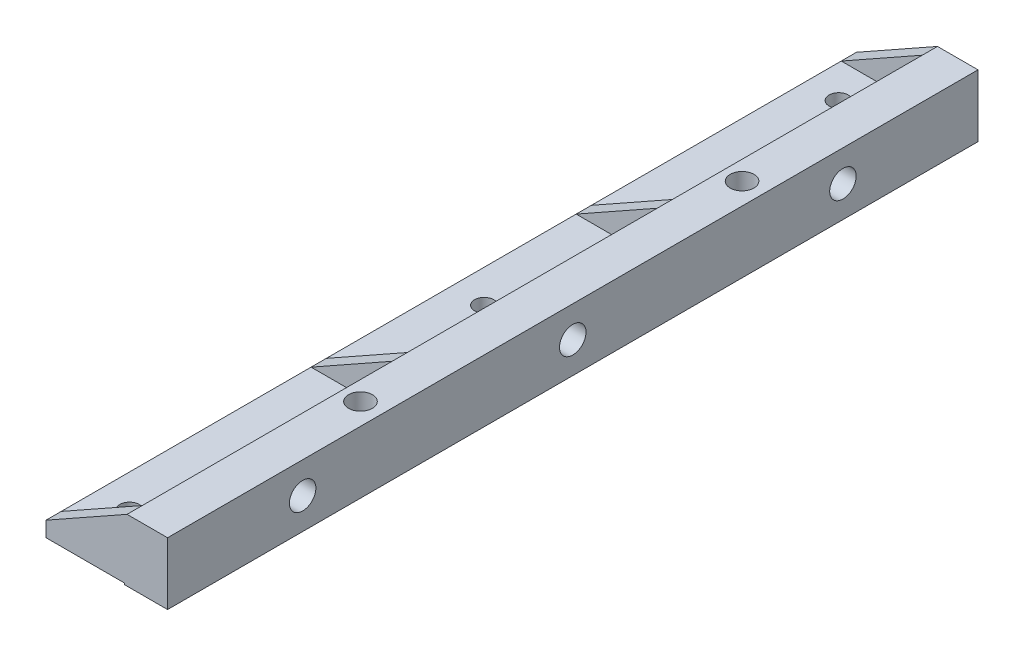
SolidWorks part; units mm, degrees
ref_plane "Front Plane" through (0, 0, 0) normal (0, 0, 1) x (1, 0, 0)
ref_plane "Top Plane" through (0, 0, 0) normal (0, 1, 0) x (1, 0, 0)
ref_plane "Right Plane" through (0, 0, 0) normal (1, 0, 0) x (0, 0, -1)
sketch "Sketch1" plane through (0, 0, 0) normal (0, 0, 1) x (1, 0, 0)
  line L0 (0, 0) -> (0, 12)
  line L1 (0, 12) -> (-8, 12)
  line L2 (-8, 12) -> (-8, 6)
  line L3 (-11, 3) -> (-24, 3)
  line L4 (-24, 3) -> (-24, 0)
  line L6 (-24, 0) -> (-8.5, 0)
  line L7 (-8.5, 0) -> (-8.5, -0.285)
  line L8 (-8.5, -0.285) -> (0, -0.285)
  line L9 (0, -0.285) -> (0, 0)
  arc A0 (-8, 6) -> (-11, 3) centre (-11, 6) cw
  dimension "D1" = 3
  dimension "D2" = 12
  dimension "D3" = 24
  dimension "D4" = 8
  dimension "D5" = 3
  dimension "D6" = 8.5
  dimension "D7" = 0.285
extrude "Boss-Extrude1" add sketch "Sketch1" along normal blind 160
ref_plane "Plane2" through (0, 0, 0) normal (0, 0, -1) x (-1, 0, 0)
ref_plane "Plane3" through (0, 0, 80) normal (0, 0, -1) x (-1, 0, 0)
ref_plane "Plane4" through (0, 0, 53.8333) normal (0, 0, -1) x (-1, 0, 0)
sketch "Sketch4" plane through (0, 0, 53.8333) normal (0, 0, -1) x (-1, 0, 0)
  line L0 (8, 12) -> (24, 3)
sketch "Sketch5" plane through (0, 0, 0) normal (0, 0, -1) x (-1, 0, 0)
  line L0 (8, 12) -> (24, 3)
rib "Rib3" sketch "Sketch4" sketch "Sketch4" thickness 3 extrusion direction parallel to sketch draft on no parameters "D1"=3
rib "Rib4" sketch "Sketch5" sketch "Sketch5" thickness 3 extrusion direction parallel to sketch draft on no parameters "D1"=3
mirror "Mirror1" about plane through (0, 0, 80) normal (0, 0, -1) of "Rib4", "Rib3"
sketch "Sketch7" plane through (0, 0, 0) normal (0, -1, 0) x (1, 0, 0)
  point P0 (-17.5001, 150)
  point P1 (-17.5001, 80)
  point P3 (-17.5001, 10)
sketch "Sketch10" plane through (0, -0.285, 0) normal (0, -1, 0) x (-1, 0, 0)
  circle A0 centre (4.25, -42.3333) radius 2.3495
  circle A1 centre (4.25, -117.6667) radius 2.3495
  point P0 (4.25, -117.6667)
  point P1 (4.25, -42.3333)
  dimension "D1" = 4.699
hole_wizard "#6 Clearance Hole1" positions "Sketch14" profile "Sketch15" hole size "#6" standard "ANSI Inch" end condition through all
sketch "Sketch14" plane through (0, 0, 0) normal (0, -1, 0) x (-1, 0, 0)
  point P0 (17.5001, -10)
  point P3 (17.5001, -80)
  point P6 (17.5001, -150)
sketch "Sketch15" plane through (-17.5001, 0, 10) normal (1, 0, 0) x (0, 0, -1)
  line L0 (0, 0) -> (0, 12)
  line L1 (0, 12) -> (1.8986, 12)
  line L2 (1.8986, 12) -> (1.8986, 0)
  line L5 (1.8986, 0) -> (0, 0)
  line L11 (0, -6.35) -> (0, 107.95) construction
  dimension "Thru Hole Dia." = 3.7973
  dimension "Thru Hole Depth" = 12
sketch "Sketch18" plane through (0, 0, 0) normal (1, 0, 0) x (0, 0, -1)
  line L0 (-160, 5.8575) -> (0, 5.8575) construction
  line L1 (-160, -0.285) -> (-160, 12) construction
  line L2 (0, -0.285) -> (0, 12) construction
  circle A0 centre (-133.3333, 5.8575) radius 2.3495
  circle A1 centre (-26.6667, 5.8575) radius 2.3495
  circle A2 centre (-80, 5.8575) radius 2.3495
  point P6 (-133.3333, 5.8575)
  point P7 (-26.6667, 5.8575)
  point P10 (-80, 5.8575)
  dimension "D3" = 4.699
  dimension "D1" = 26.6667
  dimension "D2" = 26.6667
extrude "Cut-Extrude1" cut sketch "Sketch18" against normal blind 7.5
sketch "Sketch19" plane through (0, 0, 0) normal (1, 0, 0) x (0, 0, -1)
  circle A0 centre (-133.3333, 5.8575) radius 2.6162
  circle A1 centre (-26.6667, 5.8575) radius 2.6162
  circle A2 centre (-80, 5.8575) radius 2.6162
  dimension "D1" = 5.2324
extrude "Cut-Extrude2" cut sketch "Sketch19" against normal blind 6.35
extrude "Cut-Extrude3" cut sketch "Sketch10" against normal through all
sketch "Sketch20" plane through (0, -0.285, 0) normal (0, -1, 0) x (1, 0, 0)
  circle A0 centre (-4.25, 117.6667) radius 2.6162
  circle A1 centre (-4.25, 42.3333) radius 2.6162
  dimension "D1" = 5.2324
extrude "Cut-Extrude4" cut sketch "Sketch20" against normal blind 6.35
